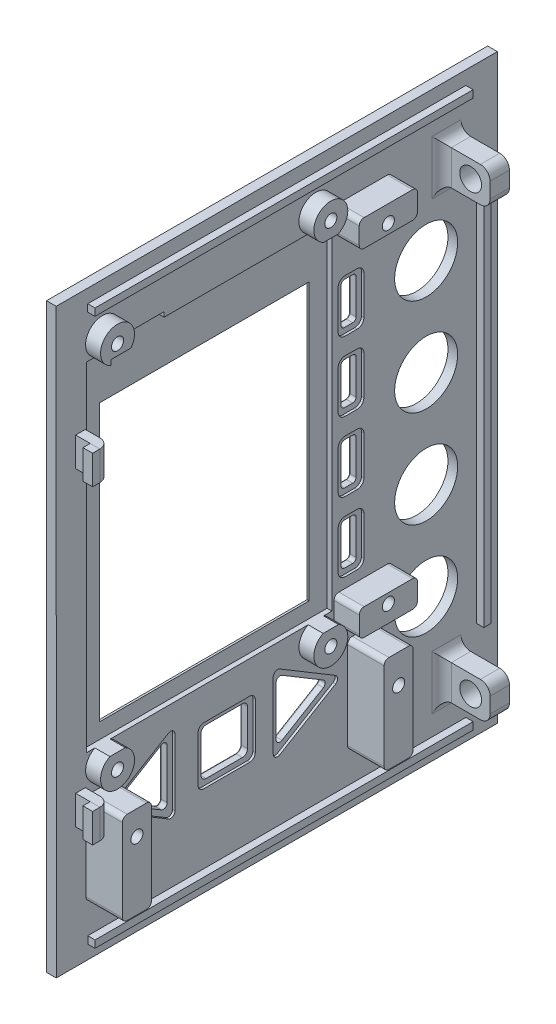
SolidWorks part; units mm, degrees
ref_plane "Front Plane" through (0, 0, 0) normal (0, 0, 1) x (1, 0, 0)
ref_plane "Top Plane" through (0, 0, 0) normal (0, 1, 0) x (1, 0, 0)
ref_plane "Right Plane" through (0, 0, 0) normal (1, 0, 0) x (0, 0, -1)
ref_plane "Plane2" through (-1175.048, -0.0877, 0) normal (-1, -0.0001, 0) x (0, 0, 1)
sketch "Sketch2" plane through (-1175.048, -0.0877, 0) normal (-1, -0.0001, 0) x (0, 0, 1)
  line L0 (-1289.195, -889.282) -> (-1289.195, -789.282) construction
  line L1 (-1204.195, -779.282) -> (-1295.195, -779.282)
  line L2 (-1204.195, -779.282) -> (-1204.195, -899.282)
  line L3 (-1204.195, -899.282) -> (-1295.195, -899.282)
  line L4 (-1295.195, -779.282) -> (-1295.195, -899.282)
  line L5 (-1289.195, -889.282) -> (-1287.685, -889.282) construction
  line L6 (-1289.195, -789.282) -> (-1287.685, -789.282) construction
  circle A0 centre (-1280.5, -869.282) radius 6.5
  circle A1 centre (-1280.5, -849.282) radius 6.5
  circle A2 centre (-1280.5, -829.282) radius 6.5
  circle A3 centre (-1280.5, -809.282) radius 6.5
  ellipse E0 centre (-1280.5, -869.282) end of major axis (-1280.4976, -868.632) minor radius 0.65 construction
  ellipse E1 centre (-1280.5, -849.282) end of major axis (-1280.4976, -848.632) minor radius 0.65 construction
  ellipse E2 centre (-1280.5, -829.282) end of major axis (-1280.4976, -828.632) minor radius 0.65 construction
  ellipse E3 centre (-1280.5, -809.282) end of major axis (-1280.4976, -808.632) minor radius 0.65 construction
  ellipse E4 centre (-1280.5, -869.282) end of major axis (-1280.4976, -868.632) minor radius 0.65
  ellipse E5 centre (-1280.5, -849.282) end of major axis (-1280.4976, -848.632) minor radius 0.65 construction
  ellipse E6 centre (-1280.5, -829.282) end of major axis (-1280.4976, -828.632) minor radius 0.65
  ellipse E7 centre (-1280.5, -809.282) end of major axis (-1280.4976, -808.632) minor radius 0.65
  dimension "D5" = 13
  dimension "D6" = 13
  dimension "D7" = 13
  dimension "D8" = 13
  dimension "D1" = 6
  dimension "D2" = 10
  dimension "D3" = 10
  dimension "D4" = 91
extrude "Boss-Extrude2" add sketch "Sketch2" along normal blind 2 contours L1 L4 L3 L2 A3 A2 A1 A0 region at (-1174.9854, -839.3697, -1248.1207)
sketch "Sketch3" plane through (-1177.048, -0.0879, 0) normal (-1, -0.0001, 0) x (0, 0, 1)
  line L12 (-1214.15, -858.982) -> (-1257.35, -858.982) construction
  line L13 (-1257.35, -858.982) -> (-1257.35, -802.002) construction
  line L14 (-1214.15, -802.002) -> (-1214.15, -858.982) construction
  line L15 (-1257.35, -802.002) -> (-1214.15, -802.002) construction
  line L16 (-1214.15, -858.982) -> (-1257.35, -858.982)
  line L17 (-1257.35, -858.982) -> (-1257.35, -802.002)
  line L18 (-1214.15, -802.002) -> (-1214.15, -858.982)
  line L19 (-1257.35, -802.002) -> (-1214.15, -802.002)
extrude "tft_cutout" cut sketch "Sketch3" against normal through all
sketch "tft_inset_cutout" plane through (-1175.048, -0.0877, 0) normal (1, 0.0001, 0) x (0, 0, -1)
  line L4 (1210.95, -792.861) -> (1210.95, -861.661) construction
  line L5 (1260.55, -792.861) -> (1210.95, -792.861) construction
  line L12 (1260.55, -861.661) -> (1260.55, -792.861) construction
  line L17 (1210.95, -861.661) -> (1260.55, -861.661) construction
  line L18 (1260.55, -861.661) -> (1260.55, -792.861) construction
  line L19 (1210.95, -861.661) -> (1260.55, -861.661) construction
  line L20 (1210.95, -792.861) -> (1210.95, -861.661) construction
  line L21 (1260.55, -792.861) -> (1210.95, -792.861) construction
  line L22 (1261.05, -792.361) -> (1210.45, -792.361)
  line L26 (1212.45, -792.861) -> (1226.45, -792.861)
  line L27 (1212.45, -792.861) -> (1212.45, -791.361)
  line L28 (1212.45, -791.361) -> (1226.45, -791.361)
  line L29 (1226.45, -792.861) -> (1226.45, -791.361)
  line L30 (1210.45, -792.361) -> (1210.45, -862.161)
  line L31 (1210.45, -862.161) -> (1261.05, -862.161)
  line L32 (1261.05, -862.161) -> (1261.05, -792.361)
  line M40 (1257.35, -858.982) -> (1214.15, -858.982)
  line M41 (1214.15, -858.982) -> (1214.15, -802.002)
  line M42 (1214.15, -802.002) -> (1257.35, -802.002)
  line M43 (1257.35, -802.002) -> (1257.35, -858.982)
  dimension "D3" = 1.5
  dimension "D4" = 0.5
  dimension "D1" = 14
  dimension "D2" = 1.5
extrude "Cut-Extrude2" cut sketch "tft_inset_cutout" against normal up to surface (1 mm away) contours L18 | L31 L32 L22 L29 L26 L27 L30 M43 M40 M41 M42 | L26 L29 L22 L27 | L22 L29 L28 L27 region at (-1174.9863, -827.3487, -1260.1879) region at (-1174.9889, -792.6987, -1219.45) region at (-1174.9889, -791.9487, -1219.45)
chamfer "Chamfer2" distance 1 angle 30 4 edges at (-1176.986, -830.5798, -1257.35) (-1176.9839, -859.0698, -1235.75) (-1176.986, -830.5798, -1214.15) (-1176.9882, -802.0898, -1235.75) first distance on face at (-1176.986, -830.5798, -1235.75)
sketch "Sketch6" plane through (-1175.048, -0.0877, 0) normal (1, 0.0001, 0) x (0, 0, -1)
  line L5 (1261.5, -864.9905) -> (1273.5, -864.9905)
  line L6 (1261.5, -864.9905) -> (1261.5, -859.4905)
  line L7 (1261.5, -859.4905) -> (1273.5, -859.4905)
  line L8 (1261.5, -864.9905) -> (1273.5, -864.9905)
  line L9 (1273.5, -864.9905) -> (1273.5, -789.9905)
  line L10 (1273.5, -789.9905) -> (1261.5, -789.9905)
  line L11 (1261.5, -789.9905) -> (1261.5, -864.9905)
  line L12 (1261.5, -864.9905) -> (1273.5, -864.9905) construction
  line L13 (1273.5, -864.9905) -> (1273.5, -789.9905) construction
  line L14 (1273.5, -789.9905) -> (1261.5, -789.9905) construction
  line L15 (1261.5, -789.9905) -> (1261.5, -864.9905) construction
  line L16 (1273.5, -864.9905) -> (1273.5, -859.4905)
  line L17 (1261.5, -789.9905) -> (1273.5, -789.9905)
  line L18 (1261.5, -789.9905) -> (1261.5, -795.4905)
  line L19 (1261.5, -795.4905) -> (1273.5, -795.4905)
  line L20 (1273.5, -789.9905) -> (1273.5, -795.4905)
  circle A0 centre (1267.5, -861.4905) radius 1.25 construction
  circle A1 centre (1267.5, -861.4905) radius 1.25 construction
  circle A2 centre (1267.5, -861.4905) radius 1.25
  circle A3 centre (1267.5, -793.4905) radius 1.25 construction
  circle A4 centre (1267.5, -793.4905) radius 1.25 construction
  circle A5 centre (1267.5, -793.4905) radius 1.25
  dimension "D2" = 2.5
  dimension "D4" = 2.5
  dimension "D3" = 2
  dimension "D5" = 2
extrude "menu_standoffs" add sketch "Sketch6" along normal up to surface (5.203 mm away)
fillet "Fillet1" radius 1 8 edges at (-1172.3871, -795.578, -1261.5) (-1172.3871, -795.578, -1273.5) (-1172.3875, -790.078, -1273.5) (-1172.3875, -790.078, -1261.5) (-1172.3824, -859.578, -1273.5) (-1172.3824, -859.578, -1261.5) (-1172.382, -865.078, -1261.5) (-1172.382, -865.078, -1273.5)
sketch "Sketch7" plane through (-1169.845, -0.0873, 0) normal (1, 0.0001, 0) x (0, 0, -1)
  circle A0 centre (1267.5, -861.4905) radius 1.25 construction
  circle A1 centre (1267.5, -793.4905) radius 1.25 construction
  circle A2 centre (1267.5, -861.4905) radius 1.25
  circle A3 centre (1267.5, -793.4905) radius 1.25
extrude "menu_standoff_holes" [suppressed] cut sketch "Sketch7" against normal blind 5 contours A2
sketch "Sketch8" plane through (-1175.048, -0.0877, 0) normal (1, 0.0001, 0) x (0, 0, -1)
  circle A0 centre (1213.75, -865.282) radius 1.55 construction
  circle A1 centre (1257.75, -865.282) radius 1.55 construction
  circle A2 centre (1257.75, -789.202) radius 1.55 construction
  circle A3 centre (1213.75, -789.2023) radius 1.55 construction
  circle A4 centre (1213.75, -865.282) radius 1.55 construction
  circle A5 centre (1257.75, -865.282) radius 1.55 construction
  circle A6 centre (1257.75, -789.202) radius 1.55 construction
  circle A7 centre (1213.75, -789.2023) radius 1.55 construction
  circle A8 centre (1213.75, -789.2023) radius 3.5
  circle A9 centre (1257.75, -789.202) radius 3.5
  circle A10 centre (1257.75, -865.282) radius 3.5
  circle A11 centre (1213.75, -865.282) radius 3.5
  circle A12 centre (1213.75, -789.2023) radius 1.25
  circle A13 centre (1213.75, -865.282) radius 1.25
  circle A14 centre (1257.75, -865.282) radius 1.25
  circle A15 centre (1257.75, -789.202) radius 1.25
  dimension "D2" = 2.5
  dimension "D1" = 7
extrude "TFT_standoffs" add sketch "Sketch8" along normal up to surface (3.09 mm away)
sketch "Sketch9" plane through (-1175.048, -0.0877, 0) normal (1, 0.0001, 0) x (0, 0, -1)
  circle A0 centre (1213.75, -789.2023) radius 1.25 construction
  circle A1 centre (1213.75, -865.282) radius 1.25 construction
  circle A2 centre (1257.75, -865.282) radius 1.25 construction
  circle A3 centre (1257.75, -789.202) radius 1.25 construction
  circle A4 centre (1213.75, -789.2023) radius 1.25
  circle A5 centre (1213.75, -865.282) radius 1.25
  circle A6 centre (1257.75, -865.282) radius 1.25
  circle A7 centre (1257.75, -789.202) radius 1.25
extrude "TFT_standoff_holes" cut sketch "Sketch9" against normal offset from surface (1 mm away) 1 up to face at (-1176.986, -830.5798, -1235.75)
extrude "Cut-Extrude5" cut sketch "Sketch5<3>" along normal through all contours L31 L32 L22 L29 L26 L27 L30 M43 M40 M41 M42 | L22 L29 L28 L27 | L26 L29 L22 L27 region at (-1174.9863, -827.3487, -1260.1879) region at (-1174.9889, -792.6987, -1219.45) region at (-1174.9889, -791.9487, -1219.45)
sketch "Sketch5<3>" plane through (-1175.048, -0.0877, 0) normal (1, 0.0001, 0) x (0, 0, -1) same geometry as "tft_inset_cutout"
sketch "Sketch10" plane through (-1175.048, -0.0877, 0) normal (1, 0.0001, 0) x (0, 0, -1)
  line L0 (1267.2535, -804.997) -> (1267.2535, -812.997) construction
  line L1 (1266.2535, -813.997) -> (1263.7535, -813.997) construction
  line L2 (1262.7535, -812.997) -> (1262.7535, -804.997) construction
  line L3 (1263.7535, -803.997) -> (1266.2535, -803.997) construction
  line L4 (1267.2535, -804.997) -> (1267.2535, -812.997) construction
  line L5 (1266.2535, -813.997) -> (1263.7535, -813.997) construction
  line L6 (1262.7535, -812.997) -> (1262.7535, -804.997) construction
  line L7 (1263.7535, -803.997) -> (1266.2535, -803.997) construction
  line L8 (1267.6535, -804.997) -> (1267.6535, -812.997)
  line L9 (1266.2535, -814.397) -> (1263.7535, -814.397)
  line L10 (1262.3535, -812.997) -> (1262.3535, -804.997)
  line L11 (1263.7535, -803.597) -> (1266.2535, -803.597)
  line L12 (1267.6535, -819.327) -> (1267.6535, -827.327)
  line L13 (1266.2535, -828.727) -> (1263.7535, -828.727)
  line L14 (1262.3535, -827.327) -> (1262.3535, -819.327)
  line L15 (1263.7535, -817.927) -> (1266.2535, -817.927)
  line L16 (1267.2535, -819.327) -> (1267.2535, -827.327) construction
  line L17 (1266.2535, -828.327) -> (1263.7535, -828.327) construction
  line L18 (1262.7535, -827.327) -> (1262.7535, -819.327) construction
  line L19 (1263.7535, -818.327) -> (1266.2535, -818.327) construction
  line L20 (1267.6535, -833.657) -> (1267.6535, -841.657)
  line L21 (1266.2535, -843.057) -> (1263.7535, -843.057)
  line L22 (1262.3535, -841.657) -> (1262.3535, -833.657)
  line L23 (1263.7535, -832.257) -> (1266.2535, -832.257)
  line L24 (1267.2535, -833.657) -> (1267.2535, -841.657) construction
  line L25 (1266.2535, -842.657) -> (1263.7535, -842.657) construction
  line L26 (1262.7535, -841.657) -> (1262.7535, -833.657) construction
  line L27 (1263.7535, -832.657) -> (1266.2535, -832.657) construction
  line L28 (1267.6535, -847.987) -> (1267.6535, -855.987)
  line L29 (1266.2535, -857.387) -> (1263.7535, -857.387)
  line L30 (1262.3535, -855.987) -> (1262.3535, -847.987)
  line L31 (1263.7535, -846.587) -> (1266.2535, -846.587)
  line L32 (1267.2535, -847.987) -> (1267.2535, -855.987) construction
  line L33 (1266.2535, -856.987) -> (1263.7535, -856.987) construction
  line L34 (1262.7535, -855.987) -> (1262.7535, -847.987) construction
  line L35 (1263.7535, -846.987) -> (1266.2535, -846.987) construction
  arc A0 (1267.2535, -804.997) -> (1266.2535, -803.997) centre (1266.2535, -804.997) ccw construction
  arc A1 (1266.2535, -813.997) -> (1267.2535, -812.997) centre (1266.2535, -812.997) ccw construction
  arc A2 (1262.7535, -812.997) -> (1263.7535, -813.997) centre (1263.7535, -812.997) ccw construction
  arc A3 (1263.7535, -803.997) -> (1262.7535, -804.997) centre (1263.7535, -804.997) ccw construction
  arc A4 (1267.2535, -804.997) -> (1266.2535, -803.997) centre (1266.2535, -804.997) ccw construction
  arc A5 (1266.2535, -813.997) -> (1267.2535, -812.997) centre (1266.2535, -812.997) ccw construction
  arc A6 (1262.7535, -812.997) -> (1263.7535, -813.997) centre (1263.7535, -812.997) ccw construction
  arc A7 (1263.7535, -803.997) -> (1262.7535, -804.997) centre (1263.7535, -804.997) ccw construction
  arc A8 (1266.2535, -814.397) -> (1267.6535, -812.997) centre (1266.2535, -812.997) ccw
  arc A9 (1262.3535, -812.997) -> (1263.7535, -814.397) centre (1263.7535, -812.997) ccw
  arc A10 (1263.7535, -803.597) -> (1262.3535, -804.997) centre (1263.7535, -804.997) ccw
  arc A11 (1267.6535, -804.997) -> (1266.2535, -803.597) centre (1266.2535, -804.997) ccw
  arc A12 (1266.2535, -828.727) -> (1267.6535, -827.327) centre (1266.2535, -827.327) ccw
  arc A13 (1262.3535, -827.327) -> (1263.7535, -828.727) centre (1263.7535, -827.327) ccw
  arc A14 (1263.7535, -817.927) -> (1262.3535, -819.327) centre (1263.7535, -819.327) ccw
  arc A15 (1267.6535, -819.327) -> (1266.2535, -817.927) centre (1266.2535, -819.327) ccw
  arc A16 (1267.2535, -819.327) -> (1266.2535, -818.327) centre (1266.2535, -819.327) ccw construction
  arc A17 (1266.2535, -828.327) -> (1267.2535, -827.327) centre (1266.2535, -827.327) ccw construction
  arc A18 (1262.7535, -827.327) -> (1263.7535, -828.327) centre (1263.7535, -827.327) ccw construction
  arc A19 (1263.7535, -818.327) -> (1262.7535, -819.327) centre (1263.7535, -819.327) ccw construction
  arc A20 (1266.2535, -843.057) -> (1267.6535, -841.657) centre (1266.2535, -841.657) ccw
  arc A21 (1262.3535, -841.657) -> (1263.7535, -843.057) centre (1263.7535, -841.657) ccw
  arc A22 (1263.7535, -832.257) -> (1262.3535, -833.657) centre (1263.7535, -833.657) ccw
  arc A23 (1267.6535, -833.657) -> (1266.2535, -832.257) centre (1266.2535, -833.657) ccw
  arc A24 (1267.2535, -833.657) -> (1266.2535, -832.657) centre (1266.2535, -833.657) ccw construction
  arc A25 (1266.2535, -842.657) -> (1267.2535, -841.657) centre (1266.2535, -841.657) ccw construction
  arc A26 (1262.7535, -841.657) -> (1263.7535, -842.657) centre (1263.7535, -841.657) ccw construction
  arc A27 (1263.7535, -832.657) -> (1262.7535, -833.657) centre (1263.7535, -833.657) ccw construction
  arc A28 (1266.2535, -857.387) -> (1267.6535, -855.987) centre (1266.2535, -855.987) ccw
  arc A29 (1262.3535, -855.987) -> (1263.7535, -857.387) centre (1263.7535, -855.987) ccw
  arc A30 (1263.7535, -846.587) -> (1262.3535, -847.987) centre (1263.7535, -847.987) ccw
  arc A31 (1267.6535, -847.987) -> (1266.2535, -846.587) centre (1266.2535, -847.987) ccw
  arc A32 (1267.2535, -847.987) -> (1266.2535, -846.987) centre (1266.2535, -847.987) ccw construction
  arc A33 (1266.2535, -856.987) -> (1267.2535, -855.987) centre (1266.2535, -855.987) ccw construction
  arc A34 (1262.7535, -855.987) -> (1263.7535, -856.987) centre (1263.7535, -855.987) ccw construction
  arc A35 (1263.7535, -846.987) -> (1262.7535, -847.987) centre (1263.7535, -847.987) ccw construction
  dimension "D1" = 0.4
  dimension "D2" = 4
extrude "menu_panel_inset" cut sketch "Sketch10" against normal offset from surface 1.5 and the other way through all up to face at (-1176.986, -830.5798, -1235.75)
sketch "Sketch11" plane through (-1177.048, -0.0879, 0) normal (-1, -0.0001, 0) x (0, 0, 1)
  line L0 (-1265.8535, -812.997) -> (-1264.1535, -812.997) construction
  line L1 (-1266.2535, -805.397) -> (-1266.2535, -812.597) construction
  line L2 (-1265.8535, -804.997) -> (-1264.1535, -804.997) construction
  line L3 (-1263.7535, -805.397) -> (-1263.7535, -812.597) construction
  line L4 (-1265.8535, -812.997) -> (-1264.1535, -812.997) construction
  line L5 (-1266.2535, -805.397) -> (-1266.2535, -812.597) construction
  line L6 (-1265.8535, -804.997) -> (-1264.1535, -804.997) construction
  line L7 (-1263.7535, -805.397) -> (-1263.7535, -812.597) construction
  line L8 (-1263.4535, -805.397) -> (-1263.4535, -812.597)
  line L9 (-1265.8535, -813.297) -> (-1264.1535, -813.297)
  line L10 (-1266.5535, -805.397) -> (-1266.5535, -812.597)
  line L11 (-1265.8535, -804.697) -> (-1264.1535, -804.697)
  line L12 (-1263.4535, -819.727) -> (-1263.4535, -826.927)
  line L13 (-1265.8535, -827.627) -> (-1264.1535, -827.627)
  line L14 (-1266.5535, -819.727) -> (-1266.5535, -826.927)
  line L15 (-1265.8535, -819.027) -> (-1264.1535, -819.027)
  line L16 (-1265.8535, -827.327) -> (-1264.1535, -827.327) construction
  line L17 (-1266.2535, -819.727) -> (-1266.2535, -826.927) construction
  line L18 (-1265.8535, -819.327) -> (-1264.1535, -819.327) construction
  line L19 (-1263.7535, -819.727) -> (-1263.7535, -826.927) construction
  line L20 (-1263.4535, -834.057) -> (-1263.4535, -841.257)
  line L21 (-1265.8535, -841.957) -> (-1264.1535, -841.957)
  line L22 (-1266.5535, -834.057) -> (-1266.5535, -841.257)
  line L23 (-1265.8535, -833.357) -> (-1264.1535, -833.357)
  line L24 (-1265.8535, -841.657) -> (-1264.1535, -841.657) construction
  line L25 (-1266.2535, -834.057) -> (-1266.2535, -841.257) construction
  line L26 (-1265.8535, -833.657) -> (-1264.1535, -833.657) construction
  line L27 (-1263.7535, -834.057) -> (-1263.7535, -841.257) construction
  line L28 (-1263.4535, -848.387) -> (-1263.4535, -855.587)
  line L29 (-1265.8535, -856.287) -> (-1264.1535, -856.287)
  line L30 (-1266.5535, -848.387) -> (-1266.5535, -855.587)
  line L31 (-1265.8535, -847.687) -> (-1264.1535, -847.687)
  line L32 (-1265.8535, -855.987) -> (-1264.1535, -855.987) construction
  line L33 (-1266.2535, -848.387) -> (-1266.2535, -855.587) construction
  line L34 (-1265.8535, -847.987) -> (-1264.1535, -847.987) construction
  line L35 (-1263.7535, -848.387) -> (-1263.7535, -855.587) construction
  arc A0 (-1264.1535, -812.997) -> (-1263.7535, -812.597) centre (-1264.1535, -812.597) ccw construction
  arc A1 (-1266.2535, -812.597) -> (-1265.8535, -812.997) centre (-1265.8535, -812.597) ccw construction
  arc A2 (-1265.8535, -804.997) -> (-1266.2535, -805.397) centre (-1265.8535, -805.397) ccw construction
  arc A3 (-1263.7535, -805.397) -> (-1264.1535, -804.997) centre (-1264.1535, -805.397) ccw construction
  arc A4 (-1264.1535, -812.997) -> (-1263.7535, -812.597) centre (-1264.1535, -812.597) ccw construction
  arc A5 (-1266.2535, -812.597) -> (-1265.8535, -812.997) centre (-1265.8535, -812.597) ccw construction
  arc A6 (-1265.8535, -804.997) -> (-1266.2535, -805.397) centre (-1265.8535, -805.397) ccw construction
  arc A7 (-1263.7535, -805.397) -> (-1264.1535, -804.997) centre (-1264.1535, -805.397) ccw construction
  arc A8 (-1264.1535, -813.297) -> (-1263.4535, -812.597) centre (-1264.1535, -812.597) ccw
  arc A9 (-1266.5535, -812.597) -> (-1265.8535, -813.297) centre (-1265.8535, -812.597) ccw
  arc A10 (-1265.8535, -804.697) -> (-1266.5535, -805.397) centre (-1265.8535, -805.397) ccw
  arc A11 (-1263.4535, -805.397) -> (-1264.1535, -804.697) centre (-1264.1535, -805.397) ccw
  arc A12 (-1264.1535, -827.627) -> (-1263.4535, -826.927) centre (-1264.1535, -826.927) ccw
  arc A13 (-1266.5535, -826.927) -> (-1265.8535, -827.627) centre (-1265.8535, -826.927) ccw
  arc A14 (-1265.8535, -819.027) -> (-1266.5535, -819.727) centre (-1265.8535, -819.727) ccw
  arc A15 (-1263.4535, -819.727) -> (-1264.1535, -819.027) centre (-1264.1535, -819.727) ccw
  arc A16 (-1264.1535, -827.327) -> (-1263.7535, -826.927) centre (-1264.1535, -826.927) ccw construction
  arc A17 (-1266.2535, -826.927) -> (-1265.8535, -827.327) centre (-1265.8535, -826.927) ccw construction
  arc A18 (-1265.8535, -819.327) -> (-1266.2535, -819.727) centre (-1265.8535, -819.727) ccw construction
  arc A19 (-1263.7535, -819.727) -> (-1264.1535, -819.327) centre (-1264.1535, -819.727) ccw construction
  arc A20 (-1264.1535, -841.957) -> (-1263.4535, -841.257) centre (-1264.1535, -841.257) ccw
  arc A21 (-1266.5535, -841.257) -> (-1265.8535, -841.957) centre (-1265.8535, -841.257) ccw
  arc A22 (-1265.8535, -833.357) -> (-1266.5535, -834.057) centre (-1265.8535, -834.057) ccw
  arc A23 (-1263.4535, -834.057) -> (-1264.1535, -833.357) centre (-1264.1535, -834.057) ccw
  arc A24 (-1264.1535, -841.657) -> (-1263.7535, -841.257) centre (-1264.1535, -841.257) ccw construction
  arc A25 (-1266.2535, -841.257) -> (-1265.8535, -841.657) centre (-1265.8535, -841.257) ccw construction
  arc A26 (-1265.8535, -833.657) -> (-1266.2535, -834.057) centre (-1265.8535, -834.057) ccw construction
  arc A27 (-1263.7535, -834.057) -> (-1264.1535, -833.657) centre (-1264.1535, -834.057) ccw construction
  arc A28 (-1264.1535, -856.287) -> (-1263.4535, -855.587) centre (-1264.1535, -855.587) ccw
  arc A29 (-1266.5535, -855.587) -> (-1265.8535, -856.287) centre (-1265.8535, -855.587) ccw
  arc A30 (-1265.8535, -847.687) -> (-1266.5535, -848.387) centre (-1265.8535, -848.387) ccw
  arc A31 (-1263.4535, -848.387) -> (-1264.1535, -847.687) centre (-1264.1535, -848.387) ccw
  arc A32 (-1264.1535, -855.987) -> (-1263.7535, -855.587) centre (-1264.1535, -855.587) ccw construction
  arc A33 (-1266.2535, -855.587) -> (-1265.8535, -855.987) centre (-1265.8535, -855.587) ccw construction
  arc A34 (-1265.8535, -847.987) -> (-1266.2535, -848.387) centre (-1265.8535, -848.387) ccw construction
  arc A35 (-1263.7535, -848.387) -> (-1264.1535, -847.987) centre (-1264.1535, -848.387) ccw construction
  dimension "D1" = 0.3
  dimension "D2" = 4
extrude "menu_panel_cutout" cut sketch "Sketch11" against normal through all
fillet "Fillet2" radius 0.25 32 edges at (-1176.9876, -809.0848, -1263.4535) (-1176.9873, -813.1798, -1263.6586) (-1176.9873, -813.3848, -1265.0035) (-1176.9873, -813.1798, -1266.3485) (-1176.9876, -809.0848, -1266.5535) (-1176.9879, -804.9899, -1266.3485) (-1176.988, -804.7848, -1265.0035) (-1176.9862, -827.7148, -1265.0035) (-1176.9863, -827.5098, -1266.3485) (-1176.9866, -823.4148, -1266.5535) (-1176.9869, -819.3199, -1266.3485) (-1176.9869, -819.1148, -1265.0035) (-1176.9869, -819.3199, -1263.6586) (-1176.9866, -823.4148, -1263.4535) (-1176.9852, -842.0448, -1265.0035) (-1176.9852, -841.8398, -1266.3485) (-1176.9855, -837.7448, -1266.5535) (-1176.9858, -833.6499, -1266.3485) (-1176.9858, -833.4448, -1265.0035) (-1176.9858, -833.6499, -1263.6586) (-1176.9855, -837.7448, -1263.4535) (-1176.9844, -852.0748, -1263.4535) (-1176.9841, -856.1698, -1263.6586) (-1176.9841, -856.3748, -1265.0035) (-1176.9841, -856.1698, -1266.3485) (-1176.9844, -852.0748, -1266.5535) (-1176.9847, -847.9799, -1266.3485) (-1176.9847, -847.7748, -1265.0035) (-1176.9879, -804.9899, -1263.6586) (-1176.9863, -827.5098, -1263.6586) (-1176.9852, -841.8398, -1263.6586) (-1176.9847, -847.9799, -1263.6586)
sketch "Sketch12" plane through (-1175.048, -0.0877, 0) normal (1, 0.0001, 0) x (0, 0, -1)
  line L0 (1270.2797, -888.782) -> (1210.2797, -888.782) construction
  line L1 (1270.2797, -868.782) -> (1264.2797, -868.782)
  line L2 (1270.2797, -868.782) -> (1270.2797, -888.782)
  line L3 (1270.2797, -888.782) -> (1264.2797, -888.782)
  line L4 (1264.2797, -868.782) -> (1264.2797, -888.782)
  line L6 (1210.2797, -888.782) -> (1216.2797, -888.782)
  line L7 (1210.2797, -888.782) -> (1210.2797, -869.782)
  line L8 (1210.2797, -869.782) -> (1216.2797, -869.782)
  line L9 (1216.2797, -888.782) -> (1216.2797, -869.782)
  line L10 (1210.2797, -868.782) -> (1270.2797, -868.782) construction
  circle A0 centre (1267.2797, -874.782) radius 1.25
  circle A1 centre (1213.2797, -874.782) radius 1.25
  dimension "D1" = 6
  dimension "D2" = 2.5
  dimension "D4" = 2.5
  dimension "D3" = 6
  dimension "D5" = 1
extrude "selector_standoffs" add sketch "Sketch12" along normal up to surface (7.55 mm away) contours L6 L9 L8 L7 A1 | L1 L4 L3 L2 A0 region at (-1174.9824, -879.0403, -1267.2797) region at (-1174.9824, -879.5722, -1213.2797)
fillet "Fillet3" radius 1 8 edges at (-1171.2067, -888.8694, -1270.2797) (-1171.2082, -868.8694, -1270.2797) (-1171.2082, -868.8694, -1264.2797) (-1171.2067, -888.8694, -1264.2797) (-1171.2067, -888.8694, -1216.2797) (-1171.2067, -888.8694, -1210.2797) (-1171.2081, -869.8694, -1210.2797) (-1171.2081, -869.8694, -1216.2797)
sketch "Sketch13" plane through (-1175.048, -0.0877, 0) normal (1, 0.0001, 0) x (0, 0, -1)
  line L0 (1218.0014, -875.2178) -> (1226.5296, -880.3347) construction
  line L1 (1227.2868, -879.906) -> (1227.2868, -869.6722) construction
  line L2 (1226.5296, -869.2434) -> (1218.0014, -874.3603) construction
  line L3 (1234.85, -871.0391) -> (1234.85, -878.5391) construction
  line L4 (1235.6, -879.2891) -> (1243.1, -879.2891) construction
  line L5 (1243.1, -870.2891) -> (1235.6, -870.2891) construction
  line L6 (1243.85, -878.5391) -> (1243.85, -871.0391) construction
  line L7 (1259.6354, -874.3603) -> (1251.1072, -869.2434) construction
  line L8 (1250.35, -869.6722) -> (1250.35, -879.906) construction
  line L9 (1251.1072, -880.3347) -> (1259.6354, -875.2178) construction
  line L10 (1218.0014, -875.2178) -> (1226.5296, -880.3347) construction
  line L11 (1227.2868, -879.906) -> (1227.2868, -869.6722) construction
  line L12 (1226.5296, -869.2434) -> (1218.0014, -874.3603) construction
  line L13 (1234.85, -871.0391) -> (1234.85, -878.5391) construction
  line L14 (1235.6, -879.2891) -> (1243.1, -879.2891) construction
  line L15 (1243.1, -870.2891) -> (1235.6, -870.2891) construction
  line L16 (1243.85, -878.5391) -> (1243.85, -871.0391) construction
  line L17 (1259.6354, -874.3603) -> (1251.1072, -869.2434) construction
  line L18 (1250.35, -869.6722) -> (1250.35, -879.906) construction
  line L19 (1251.1072, -880.3347) -> (1259.6354, -875.2178) construction
  line L20 (1217.847, -875.4751) -> (1226.3752, -880.592)
  line L21 (1227.5868, -879.906) -> (1227.5868, -869.6722)
  line L22 (1226.3752, -868.9862) -> (1217.847, -874.1031)
  line L23 (1234.55, -871.0391) -> (1234.55, -878.5391)
  line L24 (1235.6, -879.5891) -> (1243.1, -879.5891)
  line L25 (1244.15, -878.5391) -> (1244.15, -871.0391)
  line L26 (1243.1, -869.9891) -> (1235.6, -869.9891)
  line L27 (1259.7898, -874.1031) -> (1251.2616, -868.9862)
  line L28 (1250.05, -869.6722) -> (1250.05, -879.906)
  line L29 (1251.2616, -880.592) -> (1259.7898, -875.4751)
  arc A0 (1218.0014, -874.3603) -> (1218.0014, -875.2178) centre (1218.2586, -874.7891) ccw construction
  arc A1 (1226.5296, -880.3347) -> (1227.2868, -879.906) centre (1226.7868, -879.906) ccw construction
  arc A2 (1227.2868, -869.6722) -> (1226.5296, -869.2434) centre (1226.7868, -869.6722) ccw construction
  arc A3 (1235.6, -870.2891) -> (1234.85, -871.0391) centre (1235.6, -871.0391) ccw construction
  arc A4 (1234.85, -878.5391) -> (1235.6, -879.2891) centre (1235.6, -878.5391) ccw construction
  arc A5 (1243.1, -879.2891) -> (1243.85, -878.5391) centre (1243.1, -878.5391) ccw construction
  arc A6 (1243.85, -871.0391) -> (1243.1, -870.2891) centre (1243.1, -871.0391) ccw construction
  arc A7 (1259.6354, -875.2178) -> (1259.6354, -874.3603) centre (1259.3782, -874.7891) ccw construction
  arc A8 (1251.1072, -869.2434) -> (1250.35, -869.6722) centre (1250.85, -869.6722) ccw construction
  arc A9 (1250.35, -879.906) -> (1251.1072, -880.3347) centre (1250.85, -879.906) ccw construction
  arc A10 (1218.0014, -874.3603) -> (1218.0014, -875.2178) centre (1218.2586, -874.7891) ccw construction
  arc A11 (1226.5296, -880.3347) -> (1227.2868, -879.906) centre (1226.7868, -879.906) ccw construction
  arc A12 (1227.2868, -869.6722) -> (1226.5296, -869.2434) centre (1226.7868, -869.6722) ccw construction
  arc A13 (1235.6, -870.2891) -> (1234.85, -871.0391) centre (1235.6, -871.0391) ccw construction
  arc A14 (1234.85, -878.5391) -> (1235.6, -879.2891) centre (1235.6, -878.5391) ccw construction
  arc A15 (1243.1, -879.2891) -> (1243.85, -878.5391) centre (1243.1, -878.5391) ccw construction
  arc A16 (1243.85, -871.0391) -> (1243.1, -870.2891) centre (1243.1, -871.0391) ccw construction
  arc A17 (1259.6354, -875.2178) -> (1259.6354, -874.3603) centre (1259.3782, -874.7891) ccw construction
  arc A18 (1251.1072, -869.2434) -> (1250.35, -869.6722) centre (1250.85, -869.6722) ccw construction
  arc A19 (1250.35, -879.906) -> (1251.1072, -880.3347) centre (1250.85, -879.906) ccw construction
  arc A20 (1226.3752, -880.592) -> (1227.5868, -879.906) centre (1226.7868, -879.906) ccw
  arc A21 (1227.5868, -869.6722) -> (1226.3752, -868.9862) centre (1226.7868, -869.6722) ccw
  arc A22 (1217.847, -874.1031) -> (1217.847, -875.4751) centre (1218.2586, -874.7891) ccw
  arc A23 (1234.55, -878.5391) -> (1235.6, -879.5891) centre (1235.6, -878.5391) ccw
  arc A24 (1243.1, -879.5891) -> (1244.15, -878.5391) centre (1243.1, -878.5391) ccw
  arc A25 (1244.15, -871.0391) -> (1243.1, -869.9891) centre (1243.1, -871.0391) ccw
  arc A26 (1235.6, -869.9891) -> (1234.55, -871.0391) centre (1235.6, -871.0391) ccw
  arc A27 (1251.2616, -868.9862) -> (1250.05, -869.6722) centre (1250.85, -869.6722) ccw
  arc A28 (1250.05, -879.906) -> (1251.2616, -880.592) centre (1250.85, -879.906) ccw
  arc A29 (1259.7898, -875.4751) -> (1259.7898, -874.1031) centre (1259.3782, -874.7891) ccw
  dimension "D1" = 0.3
  dimension "D2" = 0.3
  dimension "D3" = 0.3
extrude "selector_cutout" cut sketch "Sketch13" against normal through all
fillet "Fillet4" radius 0.25 20 edges at (-1176.9824, -879.6769, -1239.35) (-1176.9824, -879.3694, -1234.8575) (-1176.9827, -874.8769, -1234.55) (-1176.9831, -870.3845, -1234.8575) (-1176.9831, -870.0769, -1239.35) (-1176.9831, -870.3845, -1243.8424) (-1176.9827, -874.8769, -1244.15) (-1176.9832, -869.0639, -1250.4558) (-1176.983, -871.6325, -1255.5257) (-1176.9827, -874.8769, -1260.1782) (-1176.9825, -878.1214, -1255.5257) (-1176.9823, -880.69, -1250.4558) (-1176.9824, -879.3694, -1243.8424) (-1176.9827, -874.8769, -1250.05) (-1176.9825, -878.1214, -1222.1111) (-1176.9827, -874.8769, -1217.4586) (-1176.983, -871.6325, -1222.1111) (-1176.9832, -869.0639, -1227.181) (-1176.9827, -874.8769, -1227.5868) (-1176.9823, -880.69, -1227.181)
sketch "Sketch17" plane through (-1175.048, -0.0877, 0) normal (1, 0.0001, 0) x (0, 0, -1)
  line L18 (1220.3082, -871.8101) -> (1216.0577, -874.3603) construction
  line L19 (1216.0577, -875.2178) -> (1220.3082, -877.7681) construction
  line L20 (1220.1868, -877.5537) -> (1220.1868, -872.0244) construction
  line L21 (1228.2868, -881.6722) -> (1228.2868, -867.906) construction
  line L22 (1227.5296, -867.4772) -> (1220.4505, -871.7247) construction
  line L23 (1220.5791, -871.6891) -> (1226.1368, -871.6891) construction
  line L24 (1226.3868, -871.9391) -> (1226.3868, -877.6391) construction
  line L25 (1226.1368, -877.8891) -> (1220.5791, -877.8891) construction
  line L26 (1220.4505, -877.8535) -> (1227.5296, -882.1009) construction
  line L27 (1220.3082, -871.8101) -> (1216.0577, -874.3603) construction
  line L28 (1216.0577, -875.2178) -> (1220.3082, -877.7681) construction
  line L29 (1220.1868, -877.5537) -> (1220.1868, -872.0244) construction
  line L30 (1228.2868, -881.6722) -> (1228.2868, -867.906) construction
  line L31 (1257.3286, -877.7681) -> (1261.5791, -875.2178) construction
  line L32 (1261.5791, -874.3603) -> (1257.3286, -871.8101) construction
  line L33 (1257.45, -872.0244) -> (1257.45, -877.5537) construction
  line L34 (1249.35, -867.906) -> (1249.35, -881.6722) construction
  line L35 (1250.1072, -882.1009) -> (1257.1863, -877.8535) construction
  line L36 (1257.0577, -877.8891) -> (1251.5, -877.8891) construction
  line L37 (1251.25, -877.6391) -> (1251.25, -871.9391) construction
  line L38 (1251.5, -871.6891) -> (1257.0577, -871.6891) construction
  line L39 (1257.1863, -871.7247) -> (1250.1072, -867.4772) construction
  line L40 (1233.85, -870.0391) -> (1233.85, -879.5391) construction
  line L41 (1234.6, -880.2891) -> (1244.1, -880.2891) construction
  line L42 (1244.85, -879.5391) -> (1244.85, -870.0391) construction
  line L43 (1244.1, -869.2891) -> (1234.6, -869.2891) construction
  line L44 (1257.3286, -877.7681) -> (1261.5791, -875.2178) construction
  line L45 (1261.5791, -874.3603) -> (1257.3286, -871.8101) construction
  line L46 (1257.45, -872.0244) -> (1257.45, -877.5537) construction
  line L47 (1249.35, -867.906) -> (1249.35, -881.6722) construction
  line L48 (1250.1072, -882.1009) -> (1257.1863, -877.8535) construction
  line L49 (1257.0577, -877.8891) -> (1251.5, -877.8891) construction
  line L50 (1251.25, -877.6391) -> (1251.25, -871.9391) construction
  line L51 (1251.5, -871.6891) -> (1257.0577, -871.6891) construction
  line L52 (1257.1863, -871.7247) -> (1250.1072, -867.4772) construction
  line L53 (1233.85, -870.0391) -> (1233.85, -879.5391) construction
  line L54 (1234.6, -880.2891) -> (1244.1, -880.2891) construction
  line L55 (1244.85, -879.5391) -> (1244.85, -870.0391) construction
  line L56 (1244.1, -869.2891) -> (1234.6, -869.2891) construction
  line L57 (1257.1863, -877.8535) -> (1257.3286, -877.7681)
  line L58 (1257.3286, -871.8101) -> (1257.1863, -871.7247)
  line L59 (1227.5296, -867.4772) -> (1220.4505, -871.7247) construction
  line L60 (1220.5791, -871.6891) -> (1226.1368, -871.6891) construction
  line L61 (1226.3868, -871.9391) -> (1226.3868, -877.6391) construction
  line L62 (1226.1368, -877.8891) -> (1220.5791, -877.8891) construction
  line L63 (1220.4505, -877.8535) -> (1227.5296, -882.1009) construction
  line L64 (1220.3082, -871.8101) -> (1220.4505, -871.7247)
  line L65 (1220.4505, -877.8535) -> (1220.3082, -877.7681)
  line L66 (1257.3921, -878.1965) -> (1257.5344, -878.1111)
  line L67 (1257.5344, -871.4671) -> (1257.3921, -871.3817)
  line L68 (1220.514, -872.1531) -> (1220.6563, -872.0677)
  line L69 (1220.6563, -877.5105) -> (1220.514, -877.4251)
  line L70 (1220.1024, -871.4671) -> (1215.8519, -874.0173)
  line L71 (1215.8519, -875.5608) -> (1220.1024, -878.1111)
  line L72 (1220.5868, -877.4811) -> (1220.5868, -872.0971)
  line L73 (1220.2447, -878.1965) -> (1227.3238, -882.4439)
  line L74 (1228.6868, -881.6722) -> (1228.6868, -867.906)
  line L75 (1227.3238, -867.1342) -> (1220.2447, -871.3817)
  line L76 (1257.5344, -878.1111) -> (1261.7849, -875.5608)
  line L77 (1261.7849, -874.0173) -> (1257.5344, -871.4671)
  line L78 (1257.05, -872.0971) -> (1257.05, -877.4811)
  line L79 (1257.3921, -871.3817) -> (1250.313, -867.1342)
  line L80 (1248.95, -867.906) -> (1248.95, -881.6722)
  line L81 (1250.313, -882.4439) -> (1257.3921, -878.1965)
  line L82 (1257.0213, -877.4891) -> (1251.65, -877.4891)
  line L83 (1251.65, -877.4891) -> (1251.65, -872.0891)
  line L84 (1251.65, -872.0891) -> (1257.0213, -872.0891)
  line L85 (1233.45, -870.0391) -> (1233.45, -879.5391)
  line L86 (1234.6, -880.6891) -> (1244.1, -880.6891)
  line L87 (1245.25, -879.5391) -> (1245.25, -870.0391)
  line L88 (1244.1, -868.8891) -> (1234.6, -868.8891)
  line L89 (1220.6155, -872.0891) -> (1225.9868, -872.0891)
  line L90 (1225.9868, -872.0891) -> (1225.9868, -877.4891)
  line L91 (1225.9868, -877.4891) -> (1220.6155, -877.4891)
  line L92 (1220.1024, -878.1111) -> (1220.2447, -878.1965)
  line L93 (1220.2447, -871.3817) -> (1220.1024, -871.4671)
  arc A18 (1216.0577, -874.3603) -> (1216.0577, -875.2178) centre (1216.315, -874.7891) ccw construction
  arc A19 (1220.1868, -877.5537) -> (1220.3082, -877.7681) centre (1220.4368, -877.5537) ccw construction
  arc A20 (1220.3082, -871.8101) -> (1220.1868, -872.0244) centre (1220.4368, -872.0244) ccw construction
  arc A21 (1228.2868, -867.906) -> (1227.5296, -867.4772) centre (1227.7868, -867.906) ccw construction
  arc A22 (1220.5791, -871.6891) -> (1220.4505, -871.7247) centre (1220.5791, -871.9391) ccw construction
  arc A23 (1226.3868, -871.9391) -> (1226.1368, -871.6891) centre (1226.1368, -871.9391) ccw construction
  arc A24 (1226.1368, -877.8891) -> (1226.3868, -877.6391) centre (1226.1368, -877.6391) ccw construction
  arc A25 (1220.4505, -877.8535) -> (1220.5791, -877.8891) centre (1220.5791, -877.6391) ccw construction
  arc A26 (1227.5296, -882.1009) -> (1228.2868, -881.6722) centre (1227.7868, -881.6722) ccw construction
  arc A27 (1261.5791, -875.2178) -> (1261.5791, -874.3603) centre (1261.3218, -874.7891) ccw construction
  arc A28 (1257.45, -872.0244) -> (1257.3286, -871.8101) centre (1257.2, -872.0244) ccw construction
  arc A29 (1257.3286, -877.7681) -> (1257.45, -877.5537) centre (1257.2, -877.5537) ccw construction
  arc A30 (1249.35, -881.6722) -> (1250.1072, -882.1009) centre (1249.85, -881.6722) ccw construction
  arc A31 (1257.0577, -877.8891) -> (1257.1863, -877.8535) centre (1257.0577, -877.6391) ccw construction
  arc A32 (1251.25, -877.6391) -> (1251.5, -877.8891) centre (1251.5, -877.6391) ccw construction
  arc A33 (1251.5, -871.6891) -> (1251.25, -871.9391) centre (1251.5, -871.9391) ccw construction
  arc A34 (1257.1863, -871.7247) -> (1257.0577, -871.6891) centre (1257.0577, -871.9391) ccw construction
  arc A35 (1250.1072, -867.4772) -> (1249.35, -867.906) centre (1249.85, -867.906) ccw construction
  arc A36 (1233.85, -879.5391) -> (1234.6, -880.2891) centre (1234.6, -879.5391) ccw construction
  arc A37 (1244.1, -880.2891) -> (1244.85, -879.5391) centre (1244.1, -879.5391) ccw construction
  arc A38 (1244.85, -870.0391) -> (1244.1, -869.2891) centre (1244.1, -870.0391) ccw construction
  arc A39 (1234.6, -869.2891) -> (1233.85, -870.0391) centre (1234.6, -870.0391) ccw construction
  arc A40 (1261.5791, -875.2178) -> (1261.5791, -874.3603) centre (1261.3218, -874.7891) ccw construction
  arc A41 (1257.45, -872.0244) -> (1257.3286, -871.8101) centre (1257.2, -872.0244) ccw construction
  arc A42 (1257.3286, -877.7681) -> (1257.45, -877.5537) centre (1257.2, -877.5537) ccw construction
  arc A43 (1249.35, -881.6722) -> (1250.1072, -882.1009) centre (1249.85, -881.6722) ccw construction
  arc A44 (1257.0577, -877.8891) -> (1257.1863, -877.8535) centre (1257.0577, -877.6391) ccw construction
  arc A45 (1251.25, -877.6391) -> (1251.5, -877.8891) centre (1251.5, -877.6391) ccw construction
  arc A46 (1251.5, -871.6891) -> (1251.25, -871.9391) centre (1251.5, -871.9391) ccw construction
  arc A47 (1257.1863, -871.7247) -> (1257.0577, -871.6891) centre (1257.0577, -871.9391) ccw construction
  arc A48 (1250.1072, -867.4772) -> (1249.35, -867.906) centre (1249.85, -867.906) ccw construction
  arc A49 (1233.85, -879.5391) -> (1234.6, -880.2891) centre (1234.6, -879.5391) ccw construction
  arc A50 (1244.1, -880.2891) -> (1244.85, -879.5391) centre (1244.1, -879.5391) ccw construction
  arc A51 (1244.85, -870.0391) -> (1244.1, -869.2891) centre (1244.1, -870.0391) ccw construction
  arc A52 (1234.6, -869.2891) -> (1233.85, -870.0391) centre (1234.6, -870.0391) ccw construction
  arc A53 (1216.0577, -874.3603) -> (1216.0577, -875.2178) centre (1216.315, -874.7891) ccw construction
  arc A54 (1220.1868, -877.5537) -> (1220.3082, -877.7681) centre (1220.4368, -877.5537) ccw construction
  arc A55 (1220.3082, -871.8101) -> (1220.1868, -872.0244) centre (1220.4368, -872.0244) ccw construction
  arc A56 (1228.2868, -867.906) -> (1227.5296, -867.4772) centre (1227.7868, -867.906) ccw construction
  arc A57 (1220.5791, -871.6891) -> (1220.4505, -871.7247) centre (1220.5791, -871.9391) ccw construction
  arc A58 (1226.3868, -871.9391) -> (1226.1368, -871.6891) centre (1226.1368, -871.9391) ccw construction
  arc A59 (1226.1368, -877.8891) -> (1226.3868, -877.6391) centre (1226.1368, -877.6391) ccw construction
  arc A60 (1220.4505, -877.8535) -> (1220.5791, -877.8891) centre (1220.5791, -877.6391) ccw construction
  arc A61 (1227.5296, -882.1009) -> (1228.2868, -881.6722) centre (1227.7868, -881.6722) ccw construction
  arc A62 (1215.8519, -874.0173) -> (1215.8519, -875.5608) centre (1216.315, -874.7891) ccw
  arc A63 (1220.5868, -877.4811) -> (1220.5868, -877.4811) centre (1220.5868, -877.4811) cw
  arc A64 (1220.5868, -872.0971) -> (1220.5868, -872.0971) centre (1220.5868, -872.0971) cw
  arc A65 (1227.3238, -882.4439) -> (1228.6868, -881.6722) centre (1227.7868, -881.6722) ccw
  arc A66 (1228.6868, -867.906) -> (1227.3238, -867.1342) centre (1227.7868, -867.906) ccw
  arc A67 (1261.7849, -875.5608) -> (1261.7849, -874.0173) centre (1261.3218, -874.7891) ccw
  arc A68 (1257.05, -872.0971) -> (1257.05, -872.0971) centre (1257.05, -872.0971) cw
  arc A69 (1257.05, -877.4811) -> (1257.05, -877.4811) centre (1257.05, -877.4811) cw
  arc A70 (1250.313, -867.1342) -> (1248.95, -867.906) centre (1249.85, -867.906) ccw
  arc A71 (1248.95, -881.6722) -> (1250.313, -882.4439) centre (1249.85, -881.6722) ccw
  arc A72 (1257.0213, -877.4891) -> (1257.0213, -877.4891) centre (1257.0213, -877.4891) cw
  arc A73 (1251.65, -877.4891) -> (1251.65, -877.4891) centre (1251.65, -877.4891) ccw
  arc A74 (1251.65, -872.0891) -> (1251.65, -872.0891) centre (1251.65, -872.0891) ccw
  arc A75 (1257.0213, -872.0891) -> (1257.0213, -872.0891) centre (1257.0213, -872.0891) cw
  arc A76 (1233.45, -879.5391) -> (1234.6, -880.6891) centre (1234.6, -879.5391) ccw
  arc A77 (1244.1, -880.6891) -> (1245.25, -879.5391) centre (1244.1, -879.5391) ccw
  arc A78 (1245.25, -870.0391) -> (1244.1, -868.8891) centre (1244.1, -870.0391) ccw
  arc A79 (1234.6, -868.8891) -> (1233.45, -870.0391) centre (1234.6, -870.0391) ccw
  arc A80 (1220.6155, -872.0891) -> (1220.6155, -872.0891) centre (1220.6155, -872.0891) cw
  arc A81 (1225.9868, -872.0891) -> (1225.9868, -872.0891) centre (1225.9868, -872.0891) ccw
  arc A82 (1225.9868, -877.4891) -> (1225.9868, -877.4891) centre (1225.9868, -877.4891) ccw
  arc A83 (1220.6155, -877.4891) -> (1220.6155, -877.4891) centre (1220.6155, -877.4891) cw
  dimension "D1" = 0.4
extrude "selector_inset" cut sketch "Sketch17" against normal offset from surface 1.5 and the other way blind 2 contours L74 A66 L75 L93 L70 A62 L71 L92 L73 A65 L90 L91 L69 L72 L68 L89 | L88 A79 L85 A76 L86 A77 L87 A78 | L80 A71 L81 L66 L76 A67 L77 L67 L79 A70 | L93 L70 A62 L71 L92 L73 A65 L74 A66 L75 region at (-1174.9827, -874.8768, -1253.6613) region at (-1174.983, -871.6875, -1220.2788) region at (-1174.9827, -874.8768, -1239.35) up to face at (-1176.9827, -874.8769, -1223.9365)
sketch "Sketch18" plane through (-1175.048, -0.0877, 0) normal (1, 0.0001, 0) x (0, 0, -1)
  line L0 (1287.685, -889.282) -> (1287.685, -789.282) construction
  line L1 (1287.685, -889.282) -> (1287.685, -789.282) construction
  line L2 (1287.685, -791.682) -> (1287.685, -794.882) construction
  line L3 (1287.685, -789.682) -> (1283.685, -789.682)
  line L4 (1287.685, -789.682) -> (1287.685, -796.882)
  line L5 (1287.685, -796.882) -> (1283.685, -796.882)
  line L6 (1283.685, -789.682) -> (1283.685, -796.882)
  line L7 (1287.685, -791.682) -> (1287.685, -794.882)
  line L8 (1287.685, -883.682) -> (1287.685, -886.882) construction
  line L9 (1287.685, -883.682) -> (1287.685, -886.882)
  line L11 (1287.685, -888.882) -> (1283.685, -888.882)
  line L12 (1287.685, -888.882) -> (1287.685, -881.682)
  line L13 (1287.685, -881.682) -> (1283.685, -881.682)
  line L14 (1283.685, -888.882) -> (1283.685, -881.682)
  dimension "D1" = 2
  dimension "D2" = 2
  dimension "D3" = 4
  dimension "D4" = 2
  dimension "D5" = 2
  dimension "D6" = 4
extrude "Boss-Extrude3" add sketch "Sketch18" along normal blind 10 contours L14 L11 L12 L9 L13 | L3 L6 L5 L4 region at (-1174.9888, -793.3697, -1285.685) region at (-1174.9819, -885.3697, -1285.685)
sketch "Sketch19" plane through (0, 0, -1283.685) normal (0, 0, 1) x (1, 0, 0)
  circle A0 centre (-1168.9888, -793.3692) radius 1.6 construction
  circle A1 centre (-1168.9819, -885.3692) radius 1.6 construction
  circle A2 centre (-1168.9888, -793.3692) radius 1.6 construction
  circle A3 centre (-1168.9819, -885.3692) radius 1.6 construction
  circle A4 centre (-1168.9819, -885.3692) radius 2.25
  circle A5 centre (-1168.9888, -793.3692) radius 2.25
  dimension "D1" = 4.5
  dimension "D2" = 4.5
extrude "Cut-Extrude6" cut sketch "Sketch19" against normal through all
fillet "Fillet5" radius 2 4 edges at (-1164.9891, -789.7689, -1285.685) (-1164.9885, -796.9689, -1285.685) (-1164.9822, -881.7689, -1285.685) (-1164.9817, -888.9689, -1285.685)
sketch "Sketch23" plane through (-1175.048, -0.0877, 0) normal (1, 0.0001, 0) x (0, 0, -1)
  line L0 (1292.695, -896.782) -> (1206.695, -896.782) construction
  line L1 (1210.695, -896.482) -> (1288.695, -896.482)
  line L2 (1210.695, -896.482) -> (1210.695, -894.982)
  line L3 (1210.695, -894.982) -> (1288.695, -894.982)
  line L4 (1288.695, -896.482) -> (1288.695, -894.982)
  line L5 (1206.695, -896.782) -> (1206.695, -781.782) construction
  line L6 (1292.695, -781.782) -> (1292.695, -793.282) construction
  line L7 (1292.695, -896.782) -> (1292.695, -890.282) construction
  line L8 (1292.395, -879.282) -> (1290.895, -879.282)
  line L9 (1292.395, -879.282) -> (1292.395, -799.282)
  line L10 (1292.395, -799.282) -> (1290.895, -799.282)
  line L11 (1290.895, -879.282) -> (1290.895, -799.282)
  line L14 (1206.695, -896.782) -> (1292.695, -896.782) construction
  line L15 (1292.695, -781.782) -> (1206.695, -781.782) construction
  line L16 (1206.695, -781.782) -> (1206.695, -896.782) construction
  line L17 (1210.695, -782.082) -> (1288.695, -782.082)
  line L18 (1210.695, -782.082) -> (1210.695, -783.582)
  line L19 (1210.695, -783.582) -> (1288.695, -783.582)
  line L20 (1288.695, -782.082) -> (1288.695, -783.582)
  dimension "D1" = 0.3
  dimension "D2" = 4
  dimension "D3" = 4
  dimension "D4" = 1.5
  dimension "D5" = 0.3
  dimension "D6" = 1.5
  dimension "D7" = 17.5
  dimension "D8" = 17.5
  dimension "D9" = 4
  dimension "D10" = 4
  dimension "D11" = 0.3
  dimension "D12" = 1.5
extrude "Boss-Extrude4" add sketch "Sketch23" along normal blind 1.5
sketch "Sketch24" plane through (-1175.048, -0.0877, 0) normal (1, 0.0001, 0) x (0, 0, -1)
  line L0 (1206.695, -896.782) -> (1206.695, -781.782) construction
  line L1 (1208.195, -874.282) -> (1210.195, -874.282)
  line L2 (1208.195, -874.282) -> (1208.195, -868.282)
  line L3 (1208.195, -868.282) -> (1210.195, -868.282)
  line L4 (1210.195, -874.282) -> (1210.195, -868.282)
  line L5 (1208.195, -810.282) -> (1210.195, -810.282)
  line L6 (1208.195, -810.282) -> (1208.195, -804.282)
  line L7 (1208.195, -804.282) -> (1210.195, -804.282)
  line L8 (1210.195, -810.282) -> (1210.195, -804.282)
  line L10 (1204.195, -899.282) -> (1295.195, -899.282) construction
  line L11 (1204.195, -779.282) -> (1295.195, -779.282) construction
  dimension "D1" = 2
  dimension "D2" = 6
  dimension "D3" = 1.5
  dimension "D4" = 2
  dimension "D5" = 6
  dimension "D6" = 1.5
  dimension "D7" = 25
  dimension "D8" = 25
extrude "Boss-Extrude5" add sketch "Sketch24" along normal blind 5
sketch "Sketch25" plane through (0, 0, -1208.195) normal (0, 0, 1) x (1, 0, 0)
  line L0 (-1169.9832, -868.3693) -> (-1174.9832, -868.3697) construction
  line L1 (-1169.9828, -874.3693) -> (-1171.9828, -874.3693)
  line L2 (-1169.9828, -874.3693) -> (-1169.9828, -868.3695)
  line L3 (-1169.9828, -868.3695) -> (-1171.9828, -868.3695)
  line L4 (-1171.9828, -874.3693) -> (-1171.9828, -868.3695)
  line L5 (-1169.988, -804.3693) -> (-1174.988, -804.3697) construction
  line L6 (-1169.9875, -810.3693) -> (-1171.9875, -810.3693)
  line L7 (-1169.9875, -810.3693) -> (-1169.9875, -804.3695)
  line L8 (-1169.9875, -804.3695) -> (-1171.9875, -804.3695)
  line L9 (-1171.9875, -810.3693) -> (-1171.9875, -804.3695)
  dimension "D1" = 2
  dimension "D2" = 2
extrude "Boss-Extrude6" add sketch "Sketch25" along normal up to surface (1.5 mm away)
fillet "Fillet6" radius 2 6 edges at (-1174.9891, -789.7697, -1285.685) (-1174.9885, -796.9697, -1285.685) (-1174.9822, -881.7697, -1285.685) (-1174.9817, -888.9697, -1285.685) (-1174.9819, -885.3697, -1283.685) (-1174.9888, -793.3697, -1283.685)
fillet "Fillet7" radius 2 2 edges at (-1169.983, -871.3693, -1210.195) (-1169.9878, -807.3693, -1210.195)
equation "\"R_BNC\"= 13"
equation "\"D8@Sketch2\"=\"R_BNC\""
equation "\"D7@Sketch2\"=\"R_BNC\""
equation "\"D6@Sketch2\"=\"R_BNC\""
equation "\"D5@Sketch2\"=\"R_BNC\""
equation "\"R_m3_TAP\"= 2.5"
equation "\"D2@Sketch6\"=\"R_m3_TAP\""
equation "\"D4@Sketch6\"=\"R_m3_TAP\""
equation "\"R_TFT_mount_outer\"= 7"
equation "\"D1@Sketch8\"=\"R_TFT_mount_outer\""
equation "\"D2@Sketch8\"=\"R_m3_TAP\""
equation "\"D2@Sketch12\"=\"R_m3_TAP\""
equation "\"D4@Sketch12\"=\"R_m3_TAP\""
equation "\"R_heatinsert\"= 4.5"
equation "\"D1@Sketch19\"=\"R_heatinsert\""
equation "\"D2@Sketch19\"=\"R_heatinsert\""
